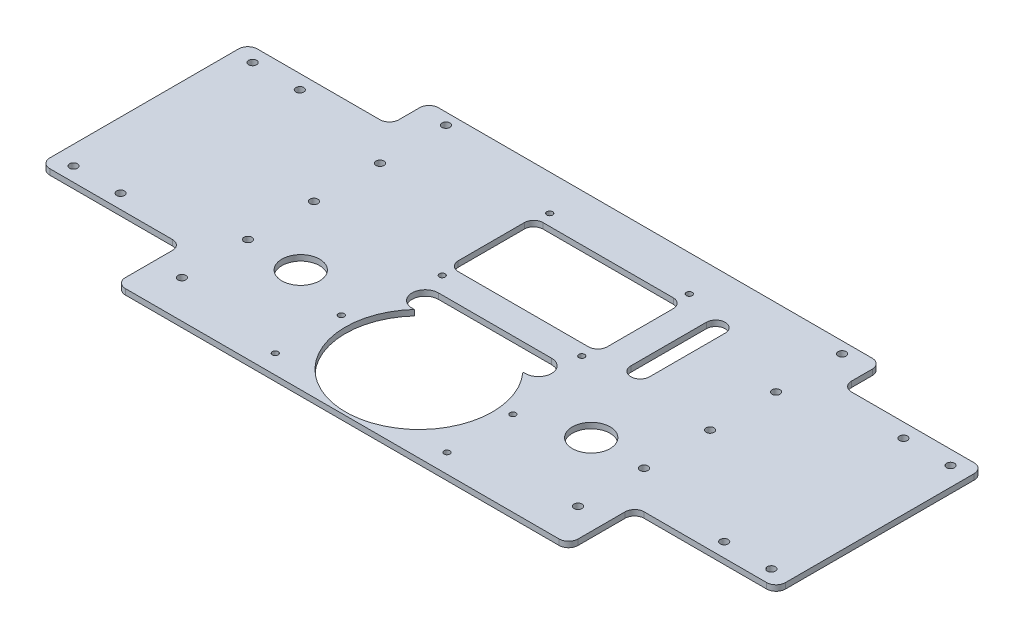
SolidWorks part; units mm, degrees
material "Thornel Mat VMA"
ref_plane "前视基准面" through (0, 0, 0) normal (0, 0, 1) x (1, 0, 0)
ref_plane "上视基准面" through (0, 0, 0) normal (0, 1, 0) x (1, 0, 0)
ref_plane "右视基准面" through (0, 0, 0) normal (1, 0, 0) x (0, 0, -1)
sketch "草图1" plane through (0, 0, 0) normal (0, 1, 0) x (1, 0, 0)
  line L0 (31.5759, -198.8718) -> (31.5759, 46.1282) construction
  line L1 (151.5759, -32.8718) -> (-88.4241, -32.8718)
  line L7 (-88.4241, -198.8718) -> (151.5759, -198.8718)
  line L8 (-88.4241, -198.8718) -> (-88.4241, -32.8718)
  line L10 (151.5759, -198.8718) -> (151.5759, -32.8718)
  line L16 (6.5759, -59.8718) -> (56.5759, -59.8718) construction
  line L18 (6.5759, -34.8718) -> (6.5759, -84.8718) construction
  line L19 (6.5759, -84.8718) -> (56.5759, -84.8718) construction
  line L20 (56.5759, -34.8718) -> (56.5759, -84.8718) construction
  line L21 (151.5759, -94.8718) -> (-88.4241, -94.8718) construction
  line L22 (-88.4241, -49.8718) -> (151.5759, -49.8718) construction
  circle A5 centre (6.5759, -84.8718) radius 1.6 construction
  circle A6 centre (56.5759, -84.8718) radius 1.6 construction
  point P6 (0, -121.2547)
  dimension "D2" = 166
  dimension "D4" = 240
  dimension "D9" = 10
  dimension "D12" = 50
  dimension "D15" = 45
extrude "构型与裁判孔" add sketch "草图1" along normal blind 3 contours L10 L21 L8 L7 region at (31.5759, 0, 115.8718)
sketch "草图4" plane through (0, 3, 0) normal (0, 1, 0) x (1, 0, 0)
  line L0 (-73.4241, -108.8718) -> (-73.4241, -198.8718) construction
  line L1 (77.0759, -32.8718) -> (77.0759, -198.8718) construction
  line L2 (151.5759, -32.8718) -> (-88.4241, -32.8718) construction
  line L3 (-88.4241, -198.8718) -> (-88.4241, -32.8718) construction
  line L4 (31.5759, -32.8718) -> (31.5759, -198.8718) construction
  line L5 (-88.4241, -198.8718) -> (151.5759, -198.8718) construction
  line L6 (-13.9241, -32.8718) -> (-13.9241, -198.8718) construction
  line L7 (-88.4241, -198.8718) -> (151.5759, -198.8718) construction
  line L8 (-88.4241, -198.8718) -> (151.5759, -198.8718) construction
  circle A0 centre (-73.4241, -73.8718) radius 2.1
  circle A1 centre (136.5759, -178.8718) radius 2.1
  circle A2 centre (-73.4241, -108.8718) radius 2.1
  circle A3 centre (-73.4241, -143.8718) radius 2.1
  circle A4 centre (-73.4241, -178.8718) radius 2.1
  circle A5 centre (136.5759, -143.8718) radius 2.1
  circle A6 centre (136.5759, -108.8718) radius 2.1
  circle A7 centre (136.5759, -73.8718) radius 2.1
  circle A8 centre (-73.4241, -38.8718) radius 2.1
  circle A9 centre (136.5759, -38.8718) radius 2.1
  circle A10 centre (77.0759, -188.8718) radius 1.55
  circle A11 centre (-13.9241, -188.8718) radius 1.55
  circle A12 centre (77.0759, -153.8718) radius 1.55
  circle A13 centre (-13.9241, -153.8718) radius 1.55
  dimension "D2" = 20
  dimension "D5" = 35
  dimension "D6" = 35
  dimension "D7" = 35
  dimension "D3" = 4.2
  dimension "D4" = 35
  dimension "D8" = 3.1
  dimension "D9" = 10
  dimension "D10" = 35
  dimension "D1" = 15
  dimension "D11" = 91
extrude "切除-拉伸3" cut sketch "草图4" against normal through all
sketch "草图5" plane through (0, 3, 0) normal (0, 1, 0) x (1, 0, 0)
  line L0 (71.0759, -57.8718) -> (-7.9241, -57.8718)
  line L1 (71.0759, -57.8718) -> (71.0759, -102.8718)
  line L2 (71.0759, -102.8718) -> (-7.9241, -102.8718)
  line L3 (-7.9241, -57.8718) -> (-7.9241, -102.8718)
  line L4 (71.0759, -57.8718) -> (-7.9241, -102.8718) construction
  line L5 (71.0759, -102.8718) -> (-7.9241, -57.8718) construction
  line L6 (31.5759, -32.8718) -> (31.5759, -104.1535) construction
  line L7 (71.0759, -80.3718) -> (-7.9241, -80.3718) construction
  line L8 (31.5759, -57.8718) -> (31.5759, -102.8718) construction
  line L9 (151.5759, -32.8718) -> (-88.4241, -32.8718) construction
  line L10 (91.0759, -100.3718) -> (91.0759, -60.3718) construction
  line L11 (86.0759, -100.3718) -> (86.0759, -60.3718)
  line L12 (96.0759, -100.3718) -> (96.0759, -60.3718)
  line L13 (31.5759, -102.8718) -> (31.5759, -198.8718) construction
  line L16 (-88.4241, -198.8718) -> (151.5759, -198.8718) construction
  line L17 (1.5759, -124.8718) -> (61.5759, -124.8718) construction
  line L18 (1.5759, -117.8718) -> (61.5759, -117.8718)
  line L19 (1.5759, -131.8718) -> (21.5759, -131.8718)
  line L20 (41.5759, -131.8718) -> (61.5759, -131.8718)
  line L21 (-73.4241, -143.8718) -> (136.5759, -143.8718) construction
  circle A0 centre (-5.4241, -51.8718) radius 1.55
  circle A1 centre (68.5759, -51.8718) radius 1.55
  circle A2 centre (68.5759, -108.8718) radius 1.55
  circle A3 centre (-5.4241, -108.8718) radius 1.55
  arc A4 (86.0759, -100.3718) -> (96.0759, -100.3718) centre (91.0759, -100.3718) ccw
  arc A5 (96.0759, -60.3718) -> (86.0759, -60.3718) centre (91.0759, -60.3718) ccw
  arc A8 (1.5759, -117.8718) -> (1.5759, -131.8718) centre (1.5759, -124.8718) ccw
  arc A9 (61.5759, -131.8718) -> (61.5759, -117.8718) centre (61.5759, -124.8718) ccw
  arc A10 (21.5759, -131.8718) -> (41.5759, -131.8718) centre (31.5759, -131.8718) ccw
  circle A11 centre (-45.4241, -143.8718) radius 10
  circle A12 centre (-73.4241, -143.8718) radius 2.1 construction
  circle A13 centre (108.5759, -143.8718) radius 10
  point P1 (110.5236, -62.9669)
  point P23 (91.0759, -80.3718)
  point P33 (31.5759, -124.8718)
  dimension "D3" = 3.1
  dimension "D7" = 5
  dimension "D10" = 7
  dimension "D13" = 20
  dimension "D14" = 28
  dimension "D1" = 79
  dimension "D2" = 45
  dimension "D4" = 37
  dimension "D5" = 28.5
  dimension "D6" = 25
  dimension "D8" = 40
  dimension "D9" = 15
  dimension "D11" = 60
  dimension "D12" = 15
extrude "切除-拉伸4" cut sketch "草图5" against normal through all
sketch "草图6" plane through (0, 0, 0) normal (0, 1, 0) x (1, 0, 0)
  line L0 (-63.0381, -108.8718) -> (146.9619, -108.8718) construction
  line L1 (-88.4241, -53.8718) -> (-163.4241, -53.8718)
  line L2 (-88.4241, -198.8718) -> (-88.4241, -32.8718) construction
  line L3 (-163.4241, -53.8718) -> (-163.4241, -163.8718)
  line L4 (-73.4241, -108.8718) -> (136.5759, -108.8718) construction
  line L5 (-88.4241, -53.8718) -> (-88.4241, -163.8718)
  line L6 (-88.4241, -163.8718) -> (-163.4241, -163.8718)
  line L7 (31.5759, -32.8718) -> (31.5759, -198.8718) construction
  line L8 (151.5759, -32.8718) -> (-88.4241, -32.8718) construction
  line L9 (-88.4241, -198.8718) -> (151.5759, -198.8718) construction
  line L10 (151.5759, -53.8718) -> (151.5759, -163.8718)
  line L11 (151.5759, -163.8718) -> (226.5759, -163.8718)
  line L12 (226.5759, -53.8718) -> (226.5759, -163.8718)
  line L13 (151.5759, -53.8718) -> (226.5759, -53.8718)
  line L14 (-153.4241, -53.8718) -> (-153.4241, -163.8718) construction
  line L15 (-128.4241, -53.8718) -> (-128.4241, -163.8718) construction
  line L16 (-153.4241, -61.3718) -> (-128.4241, -61.3718) construction
  circle A0 centre (-153.4241, -61.3718) radius 2.1
  circle A1 centre (-153.4241, -156.3718) radius 2.1
  circle A2 centre (216.5759, -156.3718) radius 2.1
  circle A3 centre (216.5759, -61.3718) radius 2.1
  circle A4 centre (-128.4241, -61.3718) radius 2.1
  circle A5 centre (-128.4241, -156.3718) radius 2.1
  circle A6 centre (191.5759, -156.3718) radius 2.1
  circle A7 centre (191.5759, -61.3718) radius 2.1
  point P15 (-88.4241, -108.8718)
  point P16 (-163.4241, -108.8718)
  dimension "D4" = 95
  dimension "D6" = 4.2
  dimension "D7" = 4.2
  dimension "D1" = 75
  dimension "D2" = 55
  dimension "D3" = 10
  dimension "D5" = 25
extrude "凸台-拉伸1" add sketch "草图6" along normal blind 3
fillet "圆角1" radius 5 18 edges at (71.0759, 1.5, 102.8718) (-7.9241, 1.5, 102.8718) (-7.9241, 1.5, 57.8718) (71.0759, 1.5, 57.8718) (151.5759, 1.5, 32.8718) (-88.4241, 1.5, 32.8718) (151.5759, 1.5, 53.8718) (151.5759, 1.5, 163.8718) (-88.4241, 1.5, 163.8718) (-88.4241, 1.5, 53.8718) (226.5759, 1.5, 53.8718) (226.5759, 1.5, 163.8718) (151.5759, 1.5, 198.8718) (-88.4241, 1.5, 198.8718) (-163.4241, 1.5, 53.8718) (-163.4241, 1.5, 163.8718) (41.5759, 1.5, 131.8718) (21.5759, 1.5, 131.8718)
sketch "草图7" plane through (0, 3, 0) normal (0, 1, 0) x (1, 0, 0)
  line L0 (146.5759, -32.8718) -> (-83.4241, -32.8718) construction
  line L1 (-48.4241, -32.8718) -> (-48.4241, -82.8718)
  line L2 (-88.4241, -48.8718) -> (-88.4241, -37.8718) construction
  line L3 (-93.4241, -82.8718) -> (-48.4241, -82.8718)
  line L4 (-83.4241, -198.8718) -> (146.5759, -198.8718) construction
  line L5 (31.5759, -198.8718) -> (31.5759, 61.0332) construction
  line L6 (156.5759, -82.8718) -> (111.5759, -82.8718)
  line L7 (151.7733, -149.2908) -> (156.5759, -82.8718)
  line L8 (111.5759, -32.8718) -> (111.5759, -82.8718)
  line L10 (-48.4241, -32.8718) -> (111.5759, -32.8718)
  line L11 (-93.4241, -82.8718) -> (156.5759, -82.8718)
  line L12 (-93.4241, -82.8718) -> (-93.4241, -208.1915)
  line L13 (-93.4241, -208.1915) -> (156.5759, -208.1915)
  line L14 (156.5759, -82.8718) -> (156.5759, -208.1915)
  line L19 (-48.4241, -32.8718) -> (-48.4241, -82.8718)
  line L20 (-48.4241, -82.8718) -> (111.5759, -82.8718)
  line L21 (111.5759, -32.8718) -> (111.5759, -82.8718)
  dimension "D1" = 50
  dimension "D2" = 40
  dimension "D3" = 0
extrude "切除-拉伸5" [suppressed] cut sketch "草图7" against normal blind 10
fillet "圆角2" [suppressed] radius 10
fillet "圆角3" [suppressed] radius 10
sketch "草图8" plane through (0, 3, 0) normal (0, 1, 0) x (1, 0, 0)
  circle A0 centre (31.5759, -158.2052) radius 35.8 construction
  circle A1 centre (31.5759, -158.2052) radius 35.8 construction
  circle A2 centre (31.5759, -158.2052) radius 39
  dimension "D1" = 78
extrude "切除-拉伸6" cut sketch "草图8" against normal blind 10
